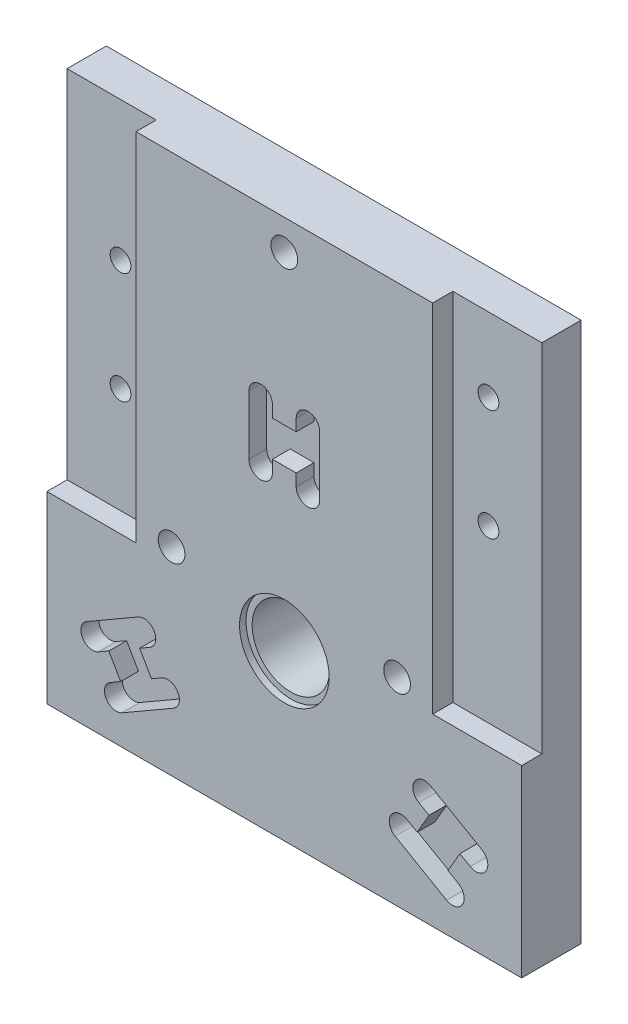
SolidWorks part; units mm, degrees
ref_plane "Front Plane" through (0, 0, 0) normal (0, 0, 1) x (1, 0, 0)
ref_plane "Top Plane" through (0, 0, 0) normal (0, 1, 0) x (1, 0, 0)
ref_plane "Right Plane" through (0, 0, 0) normal (1, 0, 0) x (0, 0, -1)
sketch "Sketch1" plane through (0, 0, 0) normal (0, 0, 1) x (1, 0, 0)
  line L0 (0, 0) -> (-50000, 0) construction
  line L1 (-40, 63.3) -> (40, 63.3)
  line L2 (-40, 63.3) -> (-40, -27.7)
  line L3 (-40, -27.7) -> (40, -27.7)
  line L4 (40, 63.3) -> (40, -27.7)
  line L5 (0, 0) -> (0, 50000) construction
  dimension "D1" = 80
  dimension "D2" = 91
  dimension "D3" = 40
  dimension "D4" = 27.7
extrude "Boss-Extrude1" add sketch "Sketch1" along normal blind 10
sketch "Sketch2" plane through (0, 0, 10) normal (0, 0, 1) x (1, 0, 0)
  circle A0 centre (0, 0) radius 6.525
  dimension "D1" = 13.05
extrude "Cut-Extrude1" cut sketch "Sketch2" against normal through all
sketch "Sketch3" plane through (0, 0, 10) normal (0, 0, 1) x (1, 0, 0)
  circle A0 centre (0, 0) radius 7.55
  dimension "D1" = 15.1
extrude "Cut-Extrude2" cut sketch "Sketch3" against normal blind 1.1
sketch "Sketch4" plane through (0, 0, 10) normal (0, 0, 1) x (1, 0, 0)
  line L0 (0, 0) -> (0, 50000) construction
  line L1 (-2, 35) -> (-2, 33)
  line L2 (-2, 33) -> (2, 33)
  line L3 (2, 33) -> (2, 35)
  line L5 (5.965, 35) -> (5.965, 25)
  line L7 (2, 25) -> (2, 27)
  line L8 (2, 27) -> (-2, 27)
  line L9 (-2, 27) -> (-2, 25)
  line L11 (-5.965, 25) -> (-5.965, 35)
  line L13 (-3.9825, 35) -> (3.9825, 35) construction
  line L14 (-3.9825, 25) -> (3.9825, 25) construction
  arc A0 (2, 35) -> (5.965, 35) centre (3.9825, 35) cw
  arc A1 (-2, 35) -> (-5.965, 35) centre (-3.9825, 35) ccw
  arc A2 (-5.965, 25) -> (-2, 25) centre (-3.9825, 25) ccw
  arc A3 (2, 25) -> (5.965, 25) centre (3.9825, 25) ccw
  dimension "D1" = 10
  dimension "D2" = 6
  dimension "D3" = 2
  dimension "D4" = 2
  dimension "D5" = 4
  dimension "D6" = 3.965
  dimension "D7" = 3.965
  dimension "D8" = 27
extrude "Cut-Extrude3" cut sketch "Sketch4" against normal blind 3
ref_axis "Axis1" through (0, 0, 0) along (0, 0, 1)
pattern_circular "CirPattern1" count 3 over 360 about axis through (0, 0, 0) along (0, 0, 1) of "Cut-Extrude3"
sketch "Sketch5" plane through (0, 0, 10) normal (0, 0, 1) x (1, 0, 0)
  line L0 (0, 0) -> (0, 58.2) construction
  line L1 (-19, 5.7) -> (19, 5.7) construction
  circle A0 centre (-19, 5.7) radius 2.25
  circle A1 centre (19, 5.7) radius 2.25
  circle A2 centre (0, 58.2) radius 2.25
  dimension "D1" = 5.7
  dimension "D2" = 19
  dimension "D4" = 4.5
  dimension "D5" = 4.5
  dimension "D6" = 4.5
  dimension "D7" = 52.5
  dimension "D3" = 38
extrude "Cut-Extrude4" cut sketch "Sketch5" against normal through all
sketch "Sketch6" plane through (0, 0, 10) normal (0, 0, 1) x (1, 0, 0)
  line L1 (-40, 63.3) -> (-25, 63.3)
  line L2 (-40, 63.3) -> (-40, 3.3)
  line L3 (-40, 3.3) -> (-25, 3.3)
  line L4 (-25, 63.3) -> (-25, 3.3)
  line L5 (40, 63.3) -> (25, 63.3)
  line L6 (40, 63.3) -> (40, 3.3)
  line L7 (40, 3.3) -> (25, 3.3)
  line L8 (25, 63.3) -> (25, 3.3)
  dimension "D1" = 15
  dimension "D2" = 15
  dimension "D3" = 60
extrude "Cut-Extrude5" cut sketch "Sketch6" against normal blind 3.4
sketch "Sketch7" plane through (0, 0, 6.6) normal (0, 0, 1) x (1, 0, 0)
  line L0 (-31, 39.825) -> (-31, 21.075) construction
  line L1 (31, 50.825) -> (31, 32.075) construction
  line L2 (40, 3.3) -> (40, 63.3) construction
  line L3 (-40, 63.3) -> (-40, 3.3) construction
  circle A0 centre (-31, 21.075) radius 1.75
  circle A1 centre (-31, 39.825) radius 1.75
  circle A2 centre (31, 32.075) radius 1.75
  circle A3 centre (31, 50.825) radius 1.75
  circle A4 centre (-19, 5.7) radius 2.25 construction
  circle A5 centre (19, 5.7) radius 2.25 construction
  dimension "D5" = 3.5
  dimension "D6" = 3.5
  dimension "D7" = 3.5
  dimension "D8" = 3.5
  dimension "D9" = 15.375
  dimension "D10" = 26.375
  dimension "D1" = 18.75
  dimension "D2" = 18.75
  dimension "D3" = 9
  dimension "D4" = 9
extrude "Cut-Extrude6" cut sketch "Sketch7" against normal through all
